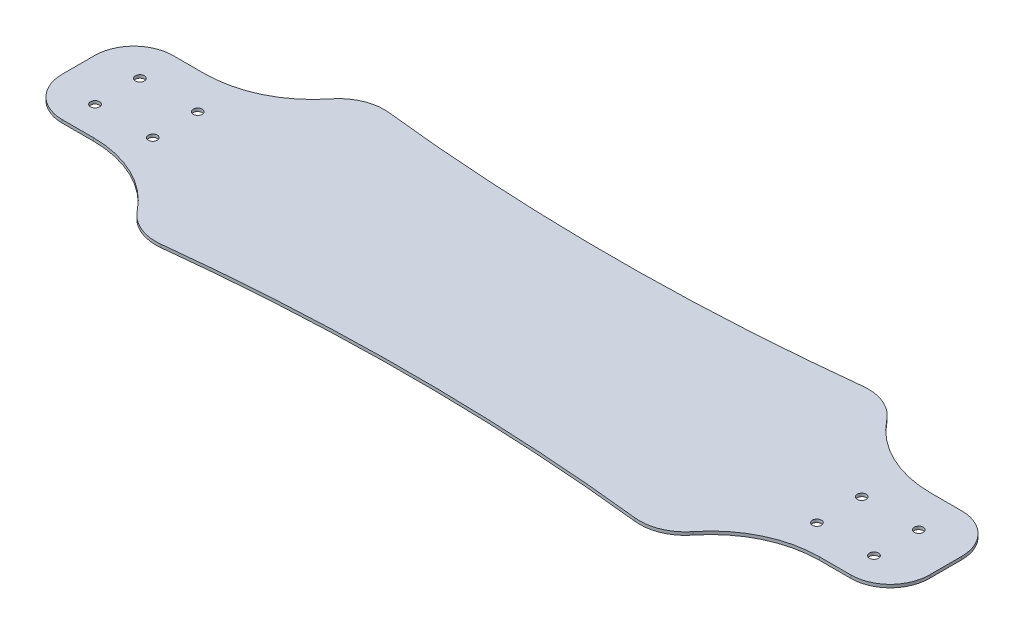
SolidWorks part; units mm, degrees
material "Maple"
ref_plane "Front Plane" through (0, 0, 0) normal (0, 0, 1) x (1, 0, 0)
ref_plane "Top Plane" through (0, 0, 0) normal (0, 1, 0) x (1, 0, 0)
ref_plane "Right Plane" through (0, 0, 0) normal (1, 0, 0) x (0, 0, -1)
sketch "Sketch1" plane through (0, 0, 0) normal (0, 1, 0) x (1, 0, 0)
  line L0 (-285.7494, 151) -> (180.9173, 151) construction
  line L1 (-350.2673, 151) -> (116.3994, 151) construction
sketch "Sketch2" plane through (0, 0, 0) normal (0, 1, 0) x (1, 0, 0)
  line L0 (377.5866, 85.3114) -> (410.0157, 85.3114)
  line L1 (450.85, 44.0973) -> (450.85, 11.1947)
  line L2 (450.85, 27.646) -> (-405.9383, 27.646) construction
  line L3 (377.5866, -30.0194) -> (410.0157, -30.0194)
  line L4 (0, 132.421) -> (0, -77.129) construction
  line L5 (-450.85, 44.0973) -> (-450.85, 11.1947)
  line L6 (-377.5866, -30.0194) -> (-410.0157, -30.0194)
  line L7 (-377.5866, 85.3114) -> (-410.0157, 85.3114)
  arc A0 (0, 132.421) -> (246.4443, 146.1466) centre (0, 2351.7477) ccw
  arc A1 (246.4443, 146.1466) -> (288.9568, 128.3511) centre (251.7075, 99.0424) cw
  arc A2 (288.9568, 128.3511) -> (377.5866, 85.3114) centre (377.5866, 198.0872) ccw
  arc A3 (410.0157, 85.3114) -> (450.85, 44.0973) centre (410.0157, 44.4754) cw
  arc A4 (410.0157, -30.0194) -> (450.85, 11.1947) centre (410.0157, 10.8166) ccw
  arc A5 (288.9568, -73.0591) -> (377.5866, -30.0194) centre (377.5866, -142.7952) cw
  arc A6 (246.4443, -90.8546) -> (288.9568, -73.0591) centre (251.7075, -43.7504) ccw
  arc A7 (0, -77.129) -> (246.4443, -90.8546) centre (0, -2296.4557) cw
  arc A8 (0, -77.129) -> (-246.4443, -90.8546) centre (0, -2296.4557) ccw
  arc A9 (-246.4443, -90.8546) -> (-288.9568, -73.0591) centre (-251.7075, -43.7504) cw
  arc A10 (-288.9568, -73.0591) -> (-377.5866, -30.0194) centre (-377.5866, -142.7952) ccw
  arc A11 (-410.0157, -30.0194) -> (-450.85, 11.1947) centre (-410.0157, 10.8166) cw
  arc A12 (-410.0157, 85.3114) -> (-450.85, 44.0973) centre (-410.0157, 44.4754) ccw
  arc A13 (-288.9568, 128.3511) -> (-377.5866, 85.3114) centre (-377.5866, 198.0872) cw
  arc A14 (-246.4443, 146.1466) -> (-288.9568, 128.3511) centre (-251.7075, 99.0424) ccw
  arc A15 (0, 132.421) -> (-246.4443, 146.1466) centre (0, 2351.7477) cw
  point P41 (-450.85, 27.646)
  point P44 (-722.2609, 345.5462)
  dimension "D3" = 40.8361
  dimension "D6" = 2219.3267
  dimension "D7" = 47.3973
  dimension "D8" = 112.7758
  dimension "D1" = 209.55
  dimension "D2" = 901.7
  dimension "D4" = 410.0157
  dimension "D5" = 16.8294
  dimension "D9" = 377.5866
extrude "Boss-Extrude1" add sketch "Sketch2" along normal blind 3.175
sketch "Sketch3" plane through (0, 0, 0) normal (0, 1, 0) x (1, 0, 0)
  circle A0 centre (-406.7398, 0.851) radius 4.6938
  circle A1 centre (-406.7398, 47.5083) radius 4.6938
  circle A2 centre (-346.6525, 0.851) radius 4.6938
  circle A3 centre (-346.6525, 47.5083) radius 4.6938
  circle A4 centre (345.3302, -0.6543) radius 4.6938
  circle A5 centre (345.3302, 46.0105) radius 4.6938
  circle A6 centre (404.656, -0.6543) radius 4.6938
  circle A7 centre (404.656, 46.0105) radius 4.6938
extrude "Cut-Extrude3" cut sketch "Sketch3" along direction (0, -1, 0) on the side of the normal through all
